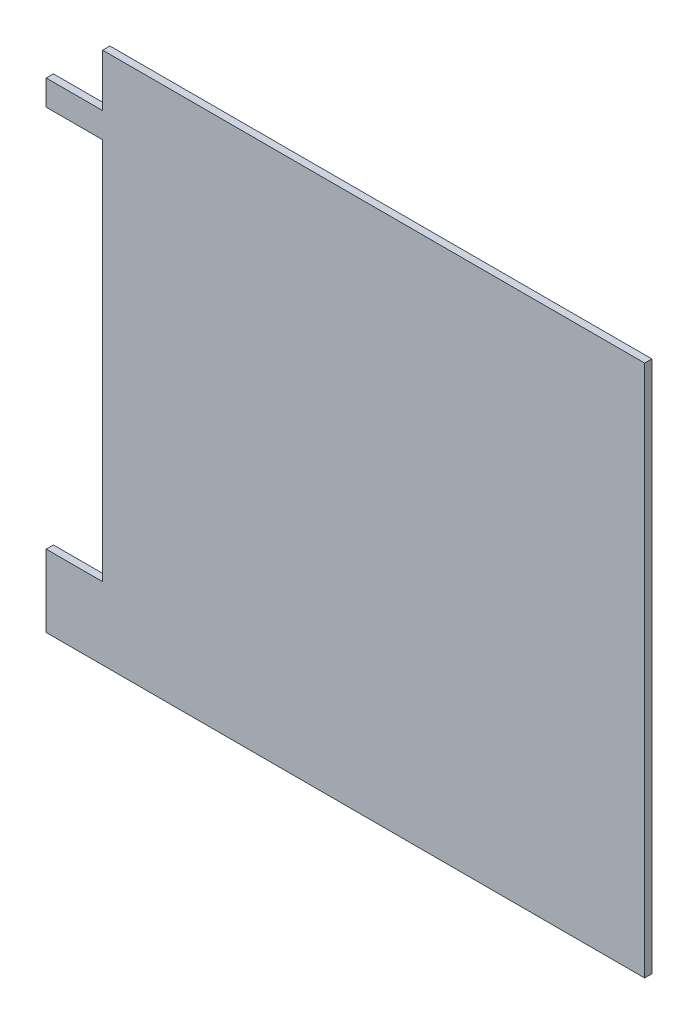
SolidWorks part; units mm, degrees
ref_plane "Front Plane" through (0, 0, 0) normal (0, 0, 1) x (1, 0, 0)
ref_plane "Top Plane" through (0, 0, 0) normal (0, 1, 0) x (1, 0, 0)
ref_plane "Right Plane" through (0, 0, 0) normal (1, 0, 0) x (0, 0, -1)
sketch "Sketch1" plane through (0, 0, 0) normal (0, 0, 1) x (1, 0, 0)
  line L0 (-5.8246, -13) -> (25.5, -13)
  line L2 (-5.8246, 1) -> (-5.8246, -13)
  line L5 (24.5, -14) -> (-24.5, -14) construction
  line L6 (325.7059, -265) -> (325.7059, 30)
  line L7 (-5.8246, -265) -> (65.6329, -265)
  line L8 (-5.8246, -265) -> (-5.8246, -225)
  line L11 (-5.8246, -265) -> (65.6329, -225) construction
  line L12 (-5.8246, -225) -> (65.6329, -265) construction
  line L15 (325.7059, -265) -> (25.5, -265)
  line L16 (25.5, 1) -> (25.5, -265)
  line L17 (-5.8246, -225) -> (25.5, -225)
  line L18 (-24.5, -224) -> (24.5, -224) construction
  line L19 (-5.8246, 1) -> (25.5, 1)
  line L20 (24.5, -224) -> (24.5, -14) construction
  line L21 (-85.2403, 31) -> (50.7059, 31) construction
  line L23 (25.5, 1) -> (25.5, 30)
  line L24 (25.5, 30) -> (325.7059, 30)
  line L27 (277.2828, 81) -> (277.2828, -319) construction
  line L28 (26.2326, -266) -> (-26.3332, -266) construction
  line L29 (50.7059, 31) -> (50.7059, -269) construction
  point P4 (32.4695, -6)
  point P10 (29.9042, -245)
  point P15 (48.1318, -132)
  point P24 (48.1318, 15.5)
  dimension "D1" = 1
  dimension "D2" = 1
  dimension "D3" = 1
  dimension "D4" = 1
  dimension "D5" = 1
  dimension "D6" = 31.3246
  dimension "D7" = 275
extrude "Boss-Extrude1" add sketch "Sketch1" along normal blind 4 contours L24 L23 L16 L7 L15 L6 | L19 L2 L0 L16 | L17 L8 L7 L16 region at (9.8377, -6, 0) region at (175.6029, -117.5, 0) region at (9.8377, -245, 0)
